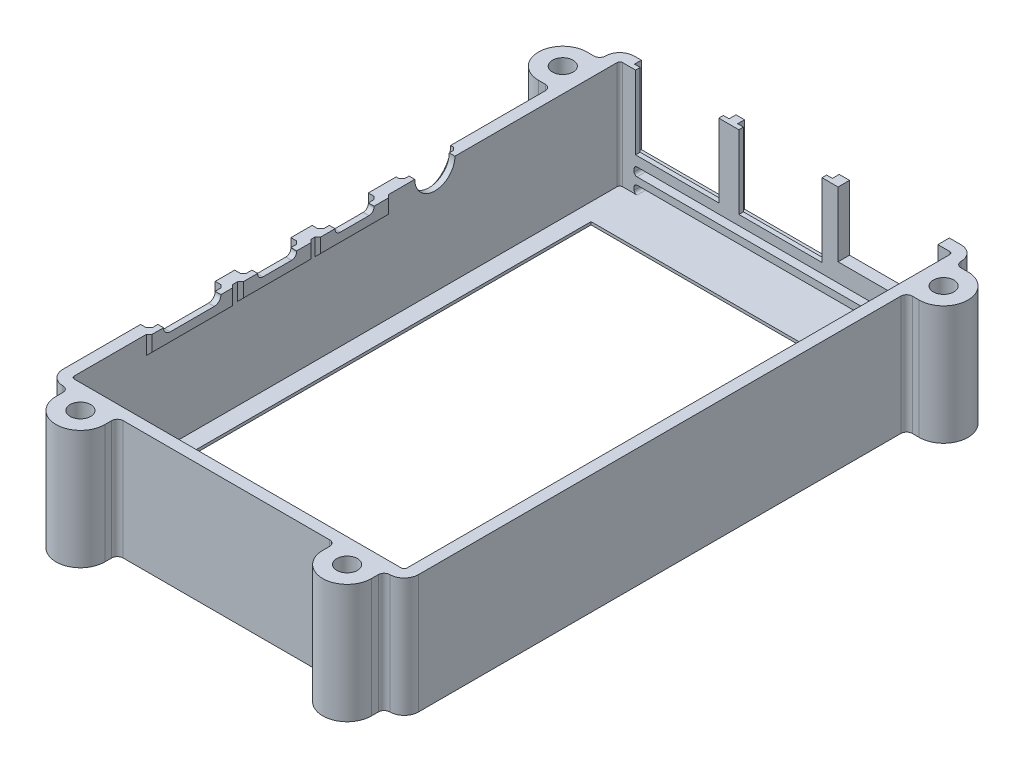
SolidWorks part; units mm, degrees
ref_plane "Front Plane" through (0, 0, 0) normal (0, 0, 1) x (1, 0, 0)
ref_plane "Top Plane" through (0, 0, 0) normal (0, 1, 0) x (1, 0, 0)
ref_plane "Right Plane" through (0, 0, 0) normal (1, 0, 0) x (0, 0, -1)
sketch "Sketch2" plane through (0, 0, 0) normal (0, 1, 0) x (1, 0, 0)
  line L1 (2.5, 0) -> (59.5, 0)
  line L2 (0, 2.5) -> (0, 97.1)
  line L3 (2.5, 99.6) -> (59.5, 99.6)
  line L4 (62, 2.5) -> (62, 97.1)
  arc A0 (0, 2.5) -> (2.5, 0) centre (2.5, 2.5) ccw
  arc A1 (59.5, 0) -> (62, 2.5) centre (59.5, 2.5) ccw
  arc A2 (62, 97.1) -> (59.5, 99.6) centre (59.5, 97.1) ccw
  arc A3 (2.5, 99.6) -> (0, 97.1) centre (2.5, 97.1) ccw
  point P7 (0, 0)
  point P10 (62, 0)
  point P13 (62, 99.6)
  point P16 (0, 99.6)
  dimension "D3" = 2.5
  dimension "D1" = 62
  dimension "D2" = 99.6
extrude "Base" add sketch "Sketch2" along normal blind 20.75
shell "Shell" thickness 2 removed face at (31, 20.75, -49.8)
sketch "Sketch14" plane through (0, 0, 0) normal (0, -1, 0) x (1, 0, 0)
  line L0 (31, 0) -> (31, -99.6) construction
  line L2 (59.5, -99.6) -> (2.5, -99.6) construction
  line L3 (-2.2, -87.6) -> (0, -87.6)
  line L4 (0, -97.1) -> (0, -2.5) construction
  line L5 (0, -87.6) -> (0, -96.1)
  line L6 (0, -96.1) -> (-2.2, -96.1)
  line L7 (3.5, 2.2) -> (3.5, 0)
  line L8 (2.5, 0) -> (59.5, 0) construction
  line L9 (3.5, 0) -> (12, 0)
  line L10 (12, 0) -> (12, 2.2)
  line L11 (64.2, -87.6) -> (62, -87.6)
  line L12 (62, -96.1) -> (64.2, -96.1)
  line L13 (62, -87.6) -> (62, -96.1)
  line L14 (50, 0) -> (50, 2.2)
  line L15 (58.5, 0) -> (50, 0)
  line L16 (58.5, 2.2) -> (58.5, 0)
  line L17 (2.5, 0) -> (59.5, 0) construction
  arc A0 (-2.2, -87.6) -> (-2.2, -96.1) centre (-2.2, -91.85) ccw
  arc A1 (3.5, 2.2) -> (12, 2.2) centre (7.75, 2.2) cw
  arc A2 (64.2, -87.6) -> (64.2, -96.1) centre (64.2, -91.85) cw
  arc A3 (58.5, 2.2) -> (50, 2.2) centre (54.25, 2.2) ccw
  dimension "D1" = 2.2
  dimension "D2" = 8.5
  dimension "D3" = 3.5
  dimension "D4" = 3.5
extrude "Clamps" add sketch "Sketch14" against normal up to surface (20.75 mm away) up to face at (31, 20.75, -49.8)
fillet "Clamp Fillets" radius 1 8 edges at (50, 10.375, 0) (58.5, 10.375, 0) (12, 10.375, 0) (3.5, 10.375, 0) (0, 10.375, -96.1) (0, 10.375, -87.6) (62, 10.375, -87.6) (62, 10.375, -96.1)
sketch "Sketch20" plane through (0, 0, 0) normal (0, -1, 0) x (1, 0, 0)
  circle A0 centre (7.75, 2.2) radius 1.8
  circle A1 centre (54.25, 2.2) radius 1.8
  circle A2 centre (64.2, -91.85) radius 1.8
  circle A3 centre (-2.2, -91.85) radius 1.8
  arc A4 (12, 2.2) -> (3.5, 2.2) centre (7.75, 2.2) ccw construction
  arc A5 (58.5, 2.2) -> (50, 2.2) centre (54.25, 2.2) ccw construction
  arc A6 (-2.2, -87.6) -> (-2.2, -96.1) centre (-2.2, -91.85) ccw construction
  arc A7 (64.2, -96.1) -> (64.2, -87.6) centre (64.2, -91.85) ccw construction
  dimension "D1" = 3.6
extrude "Clamp Holes" cut sketch "Sketch20" against normal through all
sketch "Sketch21" plane through (0, 0, 0) normal (0, -1, 0) x (1, 0, 0)
  circle A0 centre (7.75, 2.2) radius 2.9
  circle A1 centre (54.25, 2.2) radius 2.9
  circle A2 centre (64.2, -91.85) radius 2.9
  circle A3 centre (-2.2, -91.85) radius 2.9
  circle A4 centre (-2.2, -91.85) radius 1.8 construction
  circle A5 centre (7.75, 2.2) radius 1.8 construction
  circle A6 centre (54.25, 2.2) radius 1.8 construction
  circle A7 centre (64.2, -91.85) radius 1.8 construction
  dimension "D1" = 5.8
extrude "Clamp Countersinks" cut sketch "Sketch21" against normal blind 3.4
chamfer "Clamp Countersink Chamfers" distance 0.3 angle 45 4 edges at (-2.2, 0, -94.75) (64.2, 0, -94.75) (54.25, 0, -0.7) (7.75, 0, -0.7)
sketch "Sketch24" plane through (0, 0, -99.6) normal (0, 0, -1) x (-1, 0, 0)
  line L0 (-59.5, 20.75) -> (-2.5, 20.75) construction
  line L1 (-37.25, 20.75) -> (-22.75, 20.75)
  line L2 (-37.25, 20.75) -> (-37.25, 7.95)
  line L3 (-37.25, 7.95) -> (-22.75, 7.95)
  line L4 (-22.75, 20.75) -> (-22.75, 7.95)
  line L7 (-19.25, 20.75) -> (-4.75, 20.75)
  line L8 (-19.25, 20.75) -> (-19.25, 7.95)
  line L9 (-19.25, 7.95) -> (-4.75, 7.95)
  line L10 (-4.75, 20.75) -> (-4.75, 7.95)
  line L11 (-62, 20.75) -> (-62, 0) construction
  dimension "D1" = 14.5
  dimension "D2" = 42.75
  dimension "D3" = 24.75
  dimension "D4" = 12.8
extrude "USB Cutout" cut sketch "Sketch24" against normal blind 18.25
sketch "Sketch25" plane through (0, 0, -99.6) normal (0, 0, -1) x (-1, 0, 0)
  line L0 (-22.75, 20.75) -> (-19.25, 20.75) construction
  line L1 (-21.75, 20.75) -> (-38.25, 20.75)
  line L2 (-21.75, 20.75) -> (-21.75, 7.25)
  line L3 (-21.75, 7.25) -> (-38.25, 7.25)
  line L4 (-38.25, 20.75) -> (-38.25, 7.25)
  line L6 (-4.75, 20.75) -> (-2.5, 20.75) construction
  line L7 (-3.75, 20.75) -> (-20.25, 20.75)
  line L8 (-3.75, 20.75) -> (-3.75, 7.25)
  line L9 (-3.75, 7.25) -> (-20.25, 7.25)
  line L10 (-20.25, 20.75) -> (-20.25, 7.25)
  line L12 (-37.25, 20.75) -> (-37.25, 7.95) construction
  line L13 (-22.75, 7.95) -> (-22.75, 20.75) construction
  line L14 (-19.25, 20.75) -> (-19.25, 7.95) construction
  line L15 (-4.75, 7.95) -> (-4.75, 20.75) construction
  point P18 (-37.25, 14.35)
  dimension "D1" = 1
  dimension "D2" = 1
  dimension "D3" = 1
  dimension "D4" = 1
  dimension "D5" = 13.5
extrude "USB Approach" cut sketch "Sketch25" against normal blind 1.2
sketch "Sketch28" plane through (0, 0, -99.6) normal (0, 0, -1) x (-1, 0, 0)
  line L0 (-3.75, 20.75) -> (-2.5, 20.75) construction
  line L1 (-57.45, 20.75) -> (-40.05, 20.75)
  line L2 (-57.45, 20.75) -> (-57.45, 9.45)
  line L3 (-57.45, 9.45) -> (-40.05, 9.45)
  line L4 (-40.05, 20.75) -> (-40.05, 9.45)
  line L6 (-62, 20.75) -> (-62, 0) construction
  dimension "D1" = 17.4
  dimension "D2" = 4.55
  dimension "D3" = 11.3
extrude "RJ45 Cutout" cut sketch "Sketch28" against normal blind 22.7
sketch "Sketch29" plane through (2, 0, 0) normal (1, 0, 0) x (0, 0, -1)
  line L0 (97.1, 20.75) -> (2.5, 20.75) construction
  line L1 (15.05, 20.75) -> (30.05, 20.75)
  line L2 (15.05, 20.75) -> (15.05, 17.55)
  line L3 (15.05, 17.55) -> (30.05, 17.55)
  line L4 (30.05, 20.75) -> (30.05, 17.55)
  line L6 (99.6, 20.75) -> (99.6, 0) construction
  dimension "D1" = 69.55
  dimension "D2" = 15
  dimension "D5" = 3.2
extrude "USB-C Support" add sketch "Sketch29" along normal blind 0.5
chamfer "USB-C Support Chamfer" distance 0.5 angle 45 3 edges at (2.5, 19.15, -30.05) (2.5, 17.55, -22.55) (2.5, 19.15, -15.05)
sketch "Sketch30" plane through (0, 0, 0) normal (-1, 0, 0) x (0, 0, 1)
  line L0 (-86.6, 20.75) -> (-2.5, 20.75) construction
  line L6 (-29.05, 20.75) -> (-16.05, 20.75)
  line L7 (-29.05, 20.75) -> (-29.05, 18.05)
  line L8 (-29.05, 18.05) -> (-16.05, 18.05)
  line L9 (-16.05, 20.75) -> (-16.05, 18.05)
  line L10 (-99.6, 20.75) -> (-99.6, 0) construction
  dimension "D1" = 13
  dimension "D2" = 70.55
  dimension "D6" = 2.7
extrude "USB-C Approach" cut sketch "Sketch30" against normal blind 1.5
chamfer "USB-C Approach Chamfer" distance 0.5 angle 45 3 edges at (1.5, 19.4, -16.05) (1.5, 18.05, -22.55) (1.5, 19.4, -29.05)
sketch "Sketch36" plane through (0, 0, 0) normal (-1, 0, 0) x (0, 0, 1)
  line L0 (-86.6, 20.75) -> (-29.05, 20.75) construction
  line L1 (-55.75, 20.75) -> (-45.95, 20.75)
  line L2 (-55.75, 20.75) -> (-55.75, 18.27)
  line L3 (-55.75, 18.27) -> (-45.95, 18.27)
  line L4 (-45.95, 20.75) -> (-45.95, 18.27)
  line L6 (-42.25, 20.75) -> (-32.45, 20.75)
  line L7 (-42.25, 20.75) -> (-42.25, 18.27)
  line L8 (-42.25, 18.27) -> (-32.45, 18.27)
  line L9 (-32.45, 20.75) -> (-32.45, 18.27)
  line L10 (-99.6, 20.75) -> (-99.6, 0) construction
  dimension "D1" = 9.8
  dimension "D2" = 2.48
  dimension "D3" = 43.85
  dimension "D4" = 57.35
extrude "HDMI Approach" cut sketch "Sketch36" against normal blind 1.5
chamfer "HDMI Approach Chamfer" distance 0.5 angle 45 6 edges at (1.5, 19.51, -42.25) (1.5, 18.27, -37.35) (1.5, 19.51, -32.45) (1.5, 19.51, -45.95) (1.5, 18.27, -50.85) (1.5, 19.51, -55.75)
sketch "Sketch37" plane through (2, 0, 0) normal (1, 0, 0) x (0, 0, -1)
  line L0 (97.1, 20.75) -> (30.05, 20.75) construction
  line L1 (30.95, 20.75) -> (43.75, 20.75)
  line L2 (30.95, 20.75) -> (30.95, 17.77)
  line L3 (30.95, 17.77) -> (43.75, 17.77)
  line L4 (43.75, 20.75) -> (43.75, 17.77)
  line L5 (32.45, 18.27) -> (32.45, 20.75) construction
  line L6 (44.45, 20.75) -> (57.25, 20.75)
  line L7 (44.45, 20.75) -> (44.45, 17.77)
  line L8 (44.45, 17.77) -> (57.25, 17.77)
  line L9 (57.25, 20.75) -> (57.25, 17.77)
  line L10 (42.25, 20.75) -> (42.25, 18.27) construction
  line L11 (55.75, 20.75) -> (55.75, 18.27) construction
  dimension "D1" = 1.5
  dimension "D2" = 1.5
  dimension "D3" = 1.5
  dimension "D4" = 2.98
extrude "HDMI Support" add sketch "Sketch37" along normal blind 0.5
chamfer "HDMI Support Chamfer" distance 0.5 angle 45 6 edges at (2.5, 19.26, -57.25) (2.5, 17.77, -50.85) (2.5, 19.26, -44.45) (2.5, 19.26, -43.75) (2.5, 17.77, -37.35) (2.5, 19.26, -30.95)
sketch "Sketch38" plane through (1.5, 0, 0) normal (-1, 0, 0) x (0, 0, 1)
  line L0 (-46.45, 20.75) -> (-55.25, 20.75) construction
  line L1 (-54.25, 20.75) -> (-47.45, 20.75)
  line L2 (-54.25, 20.75) -> (-54.25, 20.67)
  line L3 (-53.35, 19.77) -> (-48.35, 19.77)
  line L4 (-47.45, 20.75) -> (-47.45, 20.67)
  line L5 (-32.95, 20.75) -> (-41.75, 20.75) construction
  line L6 (-40.75, 20.75) -> (-33.95, 20.75)
  line L7 (-40.75, 20.75) -> (-40.75, 20.67)
  line L8 (-39.85, 19.77) -> (-34.85, 19.77)
  line L9 (-33.95, 20.75) -> (-33.95, 20.67)
  line L10 (-16.55, 20.75) -> (-28.55, 20.75) construction
  line L11 (-27.55, 20.75) -> (-17.55, 20.75)
  line L12 (-27.55, 20.75) -> (-27.55, 20.7132)
  line L13 (-26.3868, 19.55) -> (-18.7132, 19.55)
  line L14 (-17.55, 20.75) -> (-17.55, 20.7132)
  line L15 (-45.95, 18.27) -> (-55.75, 18.27) construction
  line L16 (-55.75, 18.27) -> (-55.75, 20.75) construction
  line L17 (-45.95, 20.75) -> (-45.95, 18.27) construction
  line L18 (-42.25, 20.75) -> (-42.25, 18.27) construction
  line L19 (-16.05, 18.05) -> (-16.05, 20.75) construction
  line L20 (-29.05, 18.05) -> (-16.05, 18.05) construction
  line L21 (-29.05, 20.75) -> (-29.05, 18.05) construction
  arc A0 (-54.25, 20.67) -> (-53.35, 19.77) centre (-53.35, 20.67) ccw
  arc A1 (-48.35, 19.77) -> (-47.45, 20.67) centre (-48.35, 20.67) ccw
  arc A2 (-34.85, 19.77) -> (-33.95, 20.67) centre (-34.85, 20.67) ccw
  arc A3 (-40.75, 20.67) -> (-39.85, 19.77) centre (-39.85, 20.67) ccw
  arc A4 (-27.55, 20.7132) -> (-26.3868, 19.55) centre (-26.3868, 20.7132) ccw
  arc A5 (-18.7132, 19.55) -> (-17.55, 20.7132) centre (-18.7132, 20.7132) ccw
  dimension "D8" = 0.9
  dimension "D9" = 1.1632
  dimension "D1" = 1.5
  dimension "D2" = 1.5
  dimension "D3" = 1.5
  dimension "D4" = 1.5
  dimension "D5" = 1.5
  dimension "D6" = 1.5
  dimension "D7" = 1.5
extrude "HDMI Cutout" cut sketch "Sketch38" against normal up to surface (1 mm away) up to face at (2.5, 19.51, -50.85)
sketch "Sketch32" plane through (0, 0, 0) normal (-1, 0, 0) x (0, 0, 1)
  line L0 (-86.6, 20.75) -> (-55.75, 20.75) construction
  line L2 (-99.6, 20.75) -> (-99.6, 0) construction
  circle A0 centre (-65.35, 20.75) radius 3.5
  dimension "D1" = 7
  dimension "D2" = 34.25
extrude "Audio Cutout" cut sketch "Sketch32" against normal blind 2
sketch "Sketch33" plane through (0, 0, 0) normal (-1, 0, 0) x (0, 0, 1)
  circle A0 centre (-65.35, 20.75) radius 4.75
  arc A1 (-68.85, 20.75) -> (-61.85, 20.75) centre (-65.35, 20.75) ccw construction
  dimension "D1" = 9.5
extrude "Audio Approach" cut sketch "Sketch33" against normal blind 1
chamfer "Audio Approach Chamfer" distance 0.5 angle 45 1 edges at (1, 16, -65.35)
sketch "Sketch39" plane through (60, 0, 0) normal (-1, 0, 0) x (0, 0, 1)
  line L0 (-2.5, 2) -> (-97.1, 2) construction
  line L1 (-2, 2) -> (-10, 2)
  line L2 (-2, 2) -> (-2, 10)
  line L3 (-2, 10) -> (-10, 10) construction
  line L4 (-10, 2) -> (-10, 10) construction
  line L5 (-2, 20.75) -> (-2, 2) construction
  circle A0 centre (-10, 10) radius 8 construction
  arc A1 (-10, 2) -> (-2, 10) centre (-10, 10) ccw
  dimension "D1" = 8
extrude "Air Scoop" add sketch "Sketch39" along normal up to surface (58 mm away) up to face at (2, 17.4544, -42.9389)
sketch "Sketch41" plane through (0, 0, -99.6) normal (0, 0, -1) x (-1, 0, 0)
  line L0 (-59.5, 2) -> (-2.5, 2) construction
  line L1 (-59.5, 20.75) -> (-59.5, 0) construction
  line L2 (-2.5, 20.75) -> (-2.5, 0) construction
  line L3 (-59.5, 6.25) -> (-2.5, 6.25) construction
  line L4 (-59.5, 0) -> (-2.5, 0) construction
  line L5 (-38.25, 7.25) -> (-21.75, 7.25) construction
  line L7 (-57.5, 6.25) -> (-4.5, 6.25)
  line L8 (-57.5, 6.25) -> (-57.5, 4.75)
  line L9 (-57.5, 4.75) -> (-4.5, 4.75)
  line L10 (-4.5, 6.25) -> (-4.5, 4.75)
  line L11 (-57.5, 2) -> (-4.5, 2)
  line L12 (-57.5, 2) -> (-57.5, 3.5)
  line L13 (-57.5, 3.5) -> (-4.5, 3.5)
  line L14 (-4.5, 2) -> (-4.5, 3.5)
  dimension "D1" = 2
  dimension "D2" = 1
  dimension "D3" = 2
  dimension "D4" = 2
  dimension "D5" = 1.5
extrude "Vent" cut sketch "Sketch41" against normal blind 2
fillet "Vent Fillet" radius 0.5 8 edges at (4.5, 3.5, -98.6) (4.5, 6.25, -98.6) (4.5, 4.75, -98.6) (4.5, 2, -98.6) (57.5, 4.75, -98.6) (57.5, 2, -98.6) (57.5, 3.5, -98.6) (57.5, 6.25, -98.6)
sketch "Sketch40" plane through (0, 0, 0) normal (0, -1, 0) x (1, 0, 0)
  line L0 (59.5, -99.6) -> (2.5, -99.6) construction
  line L1 (5, -11.5823) -> (57, -11.5823)
  line L2 (5, -11.5823) -> (5, -89.5823)
  line L3 (5, -89.5823) -> (57, -89.5823)
  line L4 (57, -11.5823) -> (57, -89.5823)
  line L5 (0, -86.6) -> (0, -2.5) construction
  dimension "D1" = 10.0177
  dimension "D2" = 5
  dimension "D3" = 52
  dimension "D4" = 78
extrude "Screen Cutout" cut sketch "Sketch40" against normal through all
chamfer "Chamfer1" distance 1.5 angle 45 4 edges at (5, 0, -50.5823) (31, 0, -89.5823) (57, 0, -50.5823) (31, 0, -11.5823)
